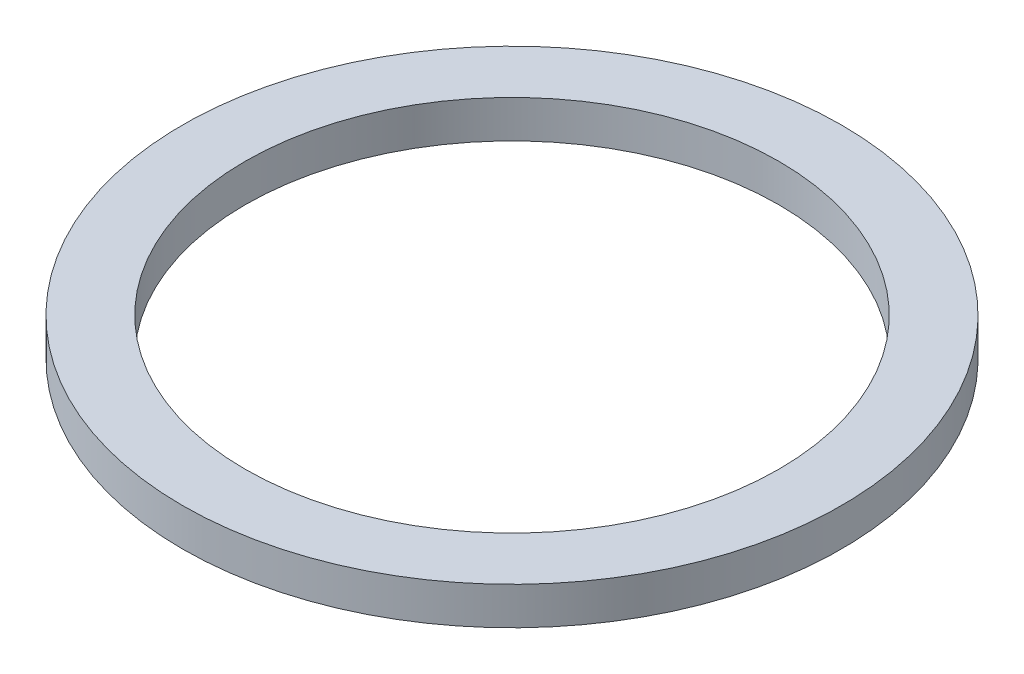
SolidWorks part; units mm, degrees
ref_plane "Front Plane" through (0, 0, 0) normal (0, 0, 1) x (1, 0, 0)
ref_plane "Top Plane" through (0, 0, 0) normal (0, 1, 0) x (1, 0, 0)
ref_plane "Right Plane" through (0, 0, 0) normal (1, 0, 0) x (0, 0, -1)
sketch "Sketch1" plane through (0, 0, 0) normal (0, 1, 0) x (1, 0, 0)
  circle A0 centre (0, 0) radius 52.5
  dimension "FLANGE_OD" = 105
extrude "Boss-Extrude1" add sketch "Sketch1" along normal blind 6
sketch "Sketch2" plane through (0, 0, 0) normal (0, 1, 0) x (1, 0, 0)
  circle A0 centre (0, 0) radius 42.5
  dimension "BORE_D" = 85
extrude "Cut-Extrude1" cut sketch "Sketch2" along normal through all
sketch "Sketch3" plane through (0, 6, 0) normal (0, 1, 0) x (1, 0, 0)
  circle A0 centre (0, 0) radius 24.4157 construction
  circle A1 centre (-24.4157, 0) radius 1.7907
  dimension "BOLT_D" = 3.5813
  dimension "BOLT_PCD" = 48.8315
extrude "Cut-Extrude2" cut sketch "Sketch3" against normal blind 4.9444 rebuild error yes
pattern_circular "CirPattern1" count 8 over 360 rebuild error yes
